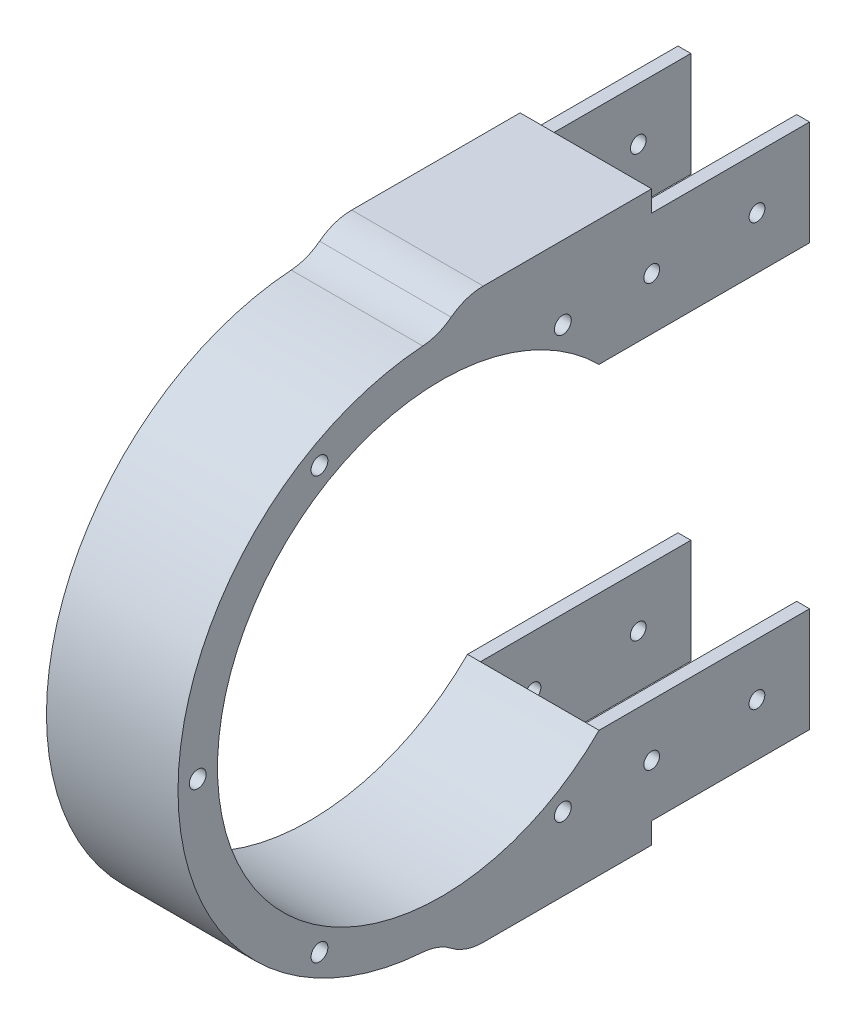
SolidWorks part; units mm, degrees
ref_plane "Front Plane" through (0, 0, 0) normal (0, 0, 1) x (1, 0, 0)
ref_plane "Top Plane" through (0, 0, 0) normal (0, 1, 0) x (1, 0, 0)
ref_plane "Right Plane" through (0, 0, 0) normal (1, 0, 0) x (0, 0, -1)
sketch "草图1" plane through (0, 0, 0) normal (1, 0, 0) x (0, 0, -1)
  line L0 (-50, 0) -> (-42.5, 0)
  line L1 (30, 30.104) -> (30, 50)
  line L2 (30, 50) -> (0, 50)
  line L3 (0, 50) -> (30, 50)
  line L4 (30, -30.104) -> (30, -50)
  line L5 (30, -50) -> (0, -50)
  arc A0 (0, 50) -> (0, -50) centre (0, 0) ccw
  arc A1 (30, 30.104) -> (30, -30.104) centre (0, 0) ccw
  circle A2 centre (-46.25, 0) radius 1.6
  circle A3 centre (-23.125, 40.0537) radius 1.6
  circle A4 centre (23.125, 40.0537) radius 1.6
  circle A6 centre (23.125, -40.0537) radius 1.6
  circle A7 centre (-23.125, -40.0537) radius 1.6
  circle A8 centre (46.25, 0) radius 1.6 [skipped]
  point P25 (0, 0)
  dimension "D1" = 100
  dimension "D2" = 85
  dimension "D3" = 3.2
  dimension "D4" = 6
extrude "凸台-拉伸1" add sketch "草图1" along normal blind 25 contours A2 L0 A1 L1 L2 A0 A4 A3 | A2 L0 A0 L5 L4 A1 A7 A6 region at (0, 2.5434, 46.25) region at (0, -0.9434, 43.575)
sketch "草图2" plane through (0, 0, -30) normal (0, 0, -1) x (-1, 0, 0)
  line L1 (-25, 50) -> (-22.55, 50)
  line L2 (-25, 50) -> (-25, 30.104)
  line L3 (-25, 30.104) -> (-22.55, 30.104)
  line L4 (-22.55, 50) -> (-22.55, 30.104)
  line L5 (-25, 30.104) -> (0, 30.104) construction
  line L6 (0, 0) -> (-70.7097, 0) construction
  line L7 (0, 50) -> (-2.45, 50)
  line L8 (0, 50) -> (0, 30.104)
  line L9 (0, 30.104) -> (-2.45, 30.104)
  line L10 (-2.45, 50) -> (-2.45, 30.104)
  line L11 (-2.45, -50) -> (-2.45, -30.104)
  line L12 (0, -30.104) -> (-2.45, -30.104)
  line L13 (0, -50) -> (0, -30.104)
  line L14 (0, -50) -> (-2.45, -50)
  line L15 (-22.55, -50) -> (-22.55, -30.104)
  line L16 (-25, -30.104) -> (-22.55, -30.104)
  line L17 (-25, -50) -> (-25, -30.104)
  line L18 (-25, -50) -> (-22.55, -50)
  dimension "D1" = 19.896
  dimension "D2" = 2.45
  dimension "D3" = 19.896
  dimension "D4" = 2.45
extrude "凸台-拉伸2" add sketch "草图2" along normal blind 40
sketch "草图3" plane through (25, 0, 0) normal (1, 0, 0) x (0, 0, -1)
  line L0 (70, -30.104) -> (70, -50) construction
  line L1 (0, 0.0089) -> (60, -0.0016) construction
  circle A0 centre (60, -40.052) radius 1.5
  circle A1 centre (40, -40.052) radius 1.5
  circle A2 centre (40.014, 40.0558) radius 1.5
  circle A3 centre (60.014, 40.0488) radius 1.5
  dimension "D1" = 3
  dimension "D2" = 3
  dimension "D3" = 10
  dimension "D4" = 20
extrude "切除-拉伸1" cut sketch "草图3" against normal through all
sketch "草图4" plane through (25, 0, 0) normal (1, 0, 0) x (0, 0, -1)
  line L0 (0, 0) -> (38.0446, 0) construction
  line L8 (40, 50) -> (40, 54)
  line L17 (0, -50) -> (40, -50)
  line L18 (0, -50) -> (0, -54)
  line L19 (0, -54) -> (40, -54)
  line L20 (40, -50) -> (40, -54)
  line L21 (0, 54) -> (40, 54)
  line L22 (0, 50) -> (0, 54)
  line L23 (0, 50) -> (40, 50)
  dimension "D1" = 4
  dimension "D2" = 40
extrude "凸台-拉伸3" add sketch "草图4" against normal blind 25
fillet "圆角4" radius 10 2 edges at (12.5, -54, 0) (12.5, 54, 0)
fillet "圆角5" radius 10 2 edges at (12.5, 50, 0) (12.5, -50, 0)
sketch "草图5" plane through (0, 50, 0) normal (0, 1, 0) x (1, 0, 0)
  line L0 (22.55, 70) -> (22.55, 40) construction
  line L1 (1.55, 40) -> (22.55, 40)
  line L2 (1.55, 40) -> (1.55, 70)
  line L3 (1.55, 70) -> (22.55, 70)
  line L4 (22.55, 40) -> (22.55, 70)
  line L5 (1.55, 40) -> (22.55, 70) construction
  line L6 (1.55, 70) -> (22.55, 40) construction
  point P0 (12.05, 55)
  dimension "D1" = 30
  dimension "D2" = 21
